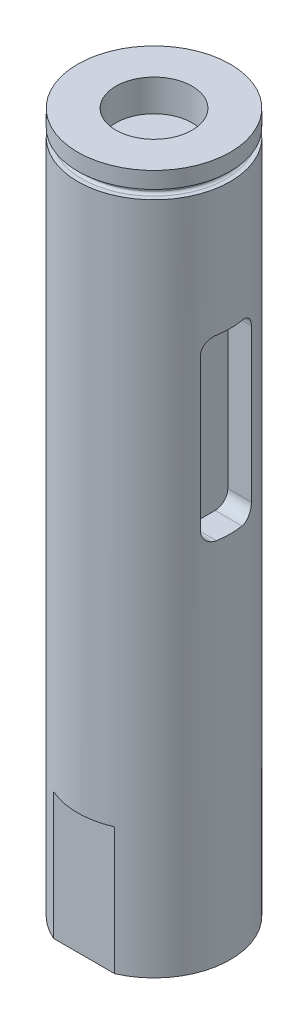
SolidWorks part; units mm, degrees
note: '?' marks a value the reader was unsure of.
ref_plane "前视基准面" through (0, 0, 0) normal (0, 0, 1) x (1, 0, 0)
ref_plane "上视基准面" through (0, 0, 0) normal (0, 1, 0) x (1, 0, 0)
ref_plane "右视基准面" through (0, 0, 0) normal (1, 0, 0) x (0, 0, -1)
sketch "Sketch1" plane through (0, 0, 0) normal (0, 1, 0) x (1, 0, 0)
  line L1 (-8.4121, 0) -> (-6, 0) construction
  line L4 (3.8, -2) -> (3.8, -4.1759) construction
  line L7 (6, 3.6442) -> (6, 2) construction
  line L8 (3.8, 4.5328) -> (3.8, 2) construction
  line L12 (3.8, 0) -> (5, 0) construction
  arc A0 (5.6569, 2) -> (5.6569, -2) centre (0, 0) ccw
  arc A1 (5.6569, 2) -> (5.6569, -2) centre (0, 0) ccw construction
  arc A2 (5.6569, -2) -> (5.6569, 2) centre (0, 0) ccw
  point P8 (7.8, 0)
  dimension "D3" = 6
extrude "Boss-Extrude1" add sketch "Sketch1" along normal blind 14
sketch "Sketch2" plane through (0, 14, 0) normal (0, 1, 0) x (1, 0, 0)
  circle A0 centre (0, 0) radius 6
  dimension "D1" = 12
extrude "Boss-Extrude2" add sketch "Sketch2" along normal blind 12
sketch "Sketch3" plane through (0, 0, 0) normal (0, -1, 0) x (1, 0, 0)
  circle A0 centre (0, 0) radius 6
  dimension "D1" = 12
extrude "Boss-Extrude3" add sketch "Sketch3" along normal blind 15
ref_plane "Plane6" through (0, 24.35, 0) normal (0, 1, 0) x (1, 0, 0)
sketch3d "3DSketch1"
  point P0 (5.8439, 5.7238, 1.3597)
ref_axis "Axis1" through (0, 26, 0) along (0, -1, 0)?
ref_plane "Plane5" through (0, 0, 0) normal (-0.2266, 0, 0.974) x (-0.2751, -0.9593, -0.064)
sketch "Groove Sketch" plane through (1.6043, 12.1829, 0.3733) normal (-0.2266, 0, 0.974) x (-0.9343, 0.2824, -0.2174)
  line L0 (10.5354, -9.9464) -> (11.9983, -9.5157)
  line L1 (11.9983, -9.5157) -> (11.8006, -8.8442)
  line L2 (11.8006, -8.8442) -> (10.3377, -9.2749)
  line L3 (10.2023, -9.5232) -> (10.2871, -9.811)
  line L4 (15.1493, -45.6204) -> (-11.9454, 46.402) construction
  line L5 (-0.273, -14.484) -> (11.2383, -11.0946) construction
  line L6 (5.4826, -12.7893) -> (-6.0977, 26.5413) construction
  arc A0 (10.2871, -9.811) -> (10.5354, -9.9464) centre (10.4789, -9.7545) ccw
  arc A1 (10.2023, -9.5232) -> (10.3377, -9.2749) centre (10.3942, -9.4668) cw
  point P10 (10.2447, -9.6671)
  dimension "Radius" = 0.2
  dimension "ID" = 10.9
  dimension "OD" = 14.35
  dimension "Width" = 0.7
  dimension "Location" = 1.65
revolve "Retaining Ring Groove" cut sketch "Groove Sketch" angle 360 about L4 reverse direction yes
other "c-ring<1>"
ref_plane "Plane7" through (6, 0, 0) normal (1, 0, 0) x (0, 0, -1)
sketch "Sketch21" plane through (6, 0, 0) normal (1, 0, 0) x (0, 0, -1)
  line L0 (0, 15.3152) -> (0, -9.2711) construction
  line L1 (-10.3418, 7) -> (16.8832, 7) construction
  line L3 (-1, 14) -> (1, 14)
  line L4 (-2, 13) -> (-2, 1)
  line L5 (-1, 0) -> (1, 0)
  line L6 (2, 13) -> (2, 1)
  line L7 (-2, 14) -> (2, 0) construction
  line L8 (-2, 0) -> (2, 14) construction
  arc A0 (1, 0) -> (2, 1) centre (1, 1) ccw
  arc A1 (-2, 1) -> (-1, 0) centre (-1, 1) ccw
  arc A2 (1, 14) -> (2, 13) centre (1, 13) cw
  arc A3 (-1, 14) -> (-2, 13) centre (-1, 13) ccw
  point P5 (0, 7)
  point P7 (0, 7)
  dimension "D3" = 1
  dimension "D1" = 7
  dimension "D2" = 4
extrude "Cut-Extrude1" cut sketch "Sketch21" against normal blind 2.2
sketch "Sketch22" plane through (0, -15, 0) normal (0, -1, 0) x (1, 0, 0)
  line L0 (-2.4688, -5.5) -> (-2.3979, -5.5) construction
  arc A1 (2.3979, -5.5) -> (-2.3979, -5.5) centre (0, 0) ccw
  arc A2 (2.3979, -5.5) -> (-2.3979, -5.5) centre (0, 0) cw
  dimension "D1" = 5.5
extrude "Boss-Extrude4" add sketch "Sketch22" along normal blind 14
ref_plane "Plane8" through (0, 0, 6) normal (0, 0, 1) x (1, 0, 0)
sketch "Sketch23" plane through (0, -29, 0) normal (0, -1, 0) x (1, 0, 0)
  line L0 (-1.9605, 5.5) -> (2.1478, 5.5) construction
  line L1 (-2.3979, 5.5) -> (2.3979, 5.5)
  circle A0 centre (0, 0) radius 6 construction
  arc A1 (2.3979, 5.5) -> (-2.3979, 5.5) centre (0, 0) ccw
  dimension "D1" = 5.5
extrude "Cut-Extrude2" cut sketch "Sketch23" against normal blind 10
sketch "Sketch24" plane through (0, 26, 0) normal (0, 1, 0) x (1, 0, 0)
  circle A0 centre (0, 0) radius 3
extrude "Cut-Extrude3" cut sketch "Sketch24" against normal blind 2.5
sketch "Sketch25" plane through (0, -29, 0) normal (0, -1, 0) x (1, 0, 0)
  point P0 (0, 0)
  point P1 (0, 0)
hole_wizard "M4 Tapped Hole1" positions "Sketch26" profile "Sketch27" tap size "M4" standard "DIN"
sketch "Sketch26" plane through (0, -29, 0) normal (0, -1, 0) x (-1, 0, 0)
  point P0 (0, 0)
cosmetic thread "Hole Thread1" parameters "D1"=9.2, "D2"=4
sketch "Sketch27" plane through (0, -29, 0) normal (1, 0, 0) x (0, 0, -1)
  line L0 (0, 0) -> (0, 10.9914)
  line L1 (0, 10.9914) -> (1.65, 10)
  line L2 (1.65, 10) -> (1.65, 0)
  line L5 (1.65, 0) -> (0, 0)
  line L10 (0, 10.9914) -> (-1.65, 10) construction
  line L11 (0, -6.35) -> (0, 107.95) construction
  dimension "Tap Drill Dia." = 3.3
  dimension "Tap Drill Depth" = 10
  dimension "Drill Angle" = 118
